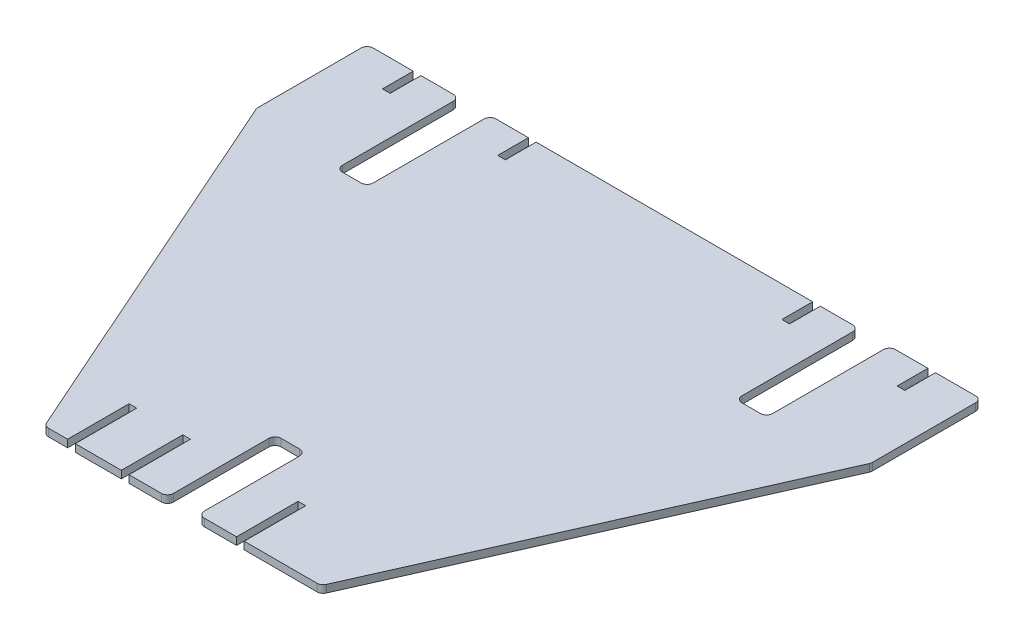
SolidWorks part; units mm, degrees
material "Corrugated Paper"
ref_plane "Front Plane" through (0, 0, 0) normal (0, 0, 1) x (1, 0, 0)
ref_plane "Top Plane" through (0, 0, 0) normal (0, 1, 0) x (1, 0, 0)
ref_plane "Right Plane" through (0, 0, 0) normal (1, 0, 0) x (0, 0, -1)
sketch "Sketch1" plane through (0, 0, 0) normal (0, 1, 0) x (1, 0, 0)
  line L0 (0, 0) -> (0, -142.875) construction
  line L1 (6.35, -57.15) -> (-6.35, -57.15)
  line L2 (-6.35, -57.15) -> (-6.35, -101.6)
  line L3 (-6.35, -101.6) -> (-22.225, -101.6)
  line L4 (-57.15, -101.6) -> (-127, 55.88)
  line L5 (-127, 55.88) -> (-127, 101.6)
  line L6 (-127, 101.6) -> (-107.95, 101.6)
  line L7 (-88.9, 101.6) -> (-88.9, 50.8)
  line L9 (-88.9, 50.8) -> (-76.2, 50.8)
  line L10 (-76.2, 50.8) -> (-76.2, 101.6)
  line L11 (-76.2, 101.6) -> (-60.325, 101.6)
  line L13 (76.2, 50.8) -> (76.2, 101.6)
  line L14 (88.9, 50.8) -> (76.2, 50.8)
  line L15 (88.9, 101.6) -> (88.9, 50.8)
  line L16 (127, 101.6) -> (107.95, 101.6)
  line L17 (127, 55.88) -> (127, 101.6)
  line L18 (57.15, -101.6) -> (127, 55.88)
  line L19 (6.35, -101.6) -> (22.225, -101.6)
  line L20 (6.35, -57.15) -> (6.35, -101.6)
  line L21 (-127, 101.6) -> (127, -101.6) construction
  line L22 (-25.4, -101.6) -> (-44.45, -101.6)
  line L24 (-25.4, -101.6) -> (-25.4, -76.2)
  line L25 (-25.4, -76.2) -> (-22.225, -76.2)
  line L26 (-22.225, -101.6) -> (-22.225, -76.2)
  line L27 (25.4, -101.6) -> (25.4, -76.2)
  line L28 (25.4, -76.2) -> (22.225, -76.2)
  line L29 (22.225, -101.6) -> (22.225, -76.2)
  line L30 (25.4, -101.6) -> (57.15, -101.6)
  line L31 (-82.55, 50.8) -> (-82.55, 101.6) construction
  line L32 (-104.775, 101.6) -> (-88.9, 101.6)
  line L34 (-107.95, 101.6) -> (-107.95, 88.9)
  line L35 (-107.95, 88.9) -> (-104.775, 88.9)
  line L36 (-104.775, 101.6) -> (-104.775, 88.9)
  line L37 (-57.15, 101.6) -> (-57.15, 88.9)
  line L38 (-57.15, 88.9) -> (-60.325, 88.9)
  line L39 (-60.325, 101.6) -> (-60.325, 88.9)
  line L40 (-57.15, 101.6) -> (57.15, 101.6)
  line L41 (107.95, 101.6) -> (107.95, 88.9)
  line L42 (107.95, 88.9) -> (104.775, 88.9)
  line L43 (104.775, 101.6) -> (104.775, 88.9)
  line L44 (57.15, 101.6) -> (57.15, 88.9)
  line L45 (60.325, 101.6) -> (60.325, 88.9)
  line L46 (57.15, 88.9) -> (60.325, 88.9)
  line L47 (60.325, 101.6) -> (76.2, 101.6)
  line L48 (104.775, 101.6) -> (88.9, 101.6)
  line L49 (-47.625, -101.6) -> (-47.625, -76.2)
  line L50 (-47.625, -76.2) -> (-44.45, -76.2)
  line L51 (-44.45, -76.2) -> (-44.45, -101.6)
  line L52 (-47.625, -101.6) -> (-57.15, -101.6)
  point P26 (0, -57.15)
  dimension "D2" = 12.7
  dimension "D3" = 254
  dimension "D5" = 44.45
  dimension "D6" = 50.8
  dimension "D7" = 203.2
  dimension "D8" = 45.72
  dimension "D10" = 3.175
  dimension "D11" = 25.4
  dimension "D12" = 3.175
  dimension "D4" = 114.3
  dimension "D13" = 50.8
  dimension "D9" = 50.8
  dimension "D14" = 38.1
  dimension "D15" = 12.7
  dimension "D16" = 19.05
extrude "Boss-Extrude1" add sketch "Sketch1" along normal blind 3.0988 contours L13 L47 L45 L46 L44 L40 L37 L38 L39 L11 L10 L9 L7 L32 L36 L35 L34 L6 L5 L4 L52 L49 L50 L51 L22 L24 L25 L26 L3 L2 L1 L20 L19 L29 L28 L27 L30 L18 L17 L16 L41 L42 L43 L48 L15 L14
fillet "Fillet1" radius 2.54 18 edges at (88.9, 1.5494, -50.8) (88.9, 1.5494, -101.6) (6.35, 1.5494, 101.6) (6.35, 1.5494, 57.15) (-6.35, 1.5494, 57.15) (-6.35, 1.5494, 101.6) (-127, 1.5494, -55.88) (-127, 1.5494, -101.6) (-88.9, 1.5494, -101.6) (-88.9, 1.5494, -50.8) (-76.2, 1.5494, -50.8) (-76.2, 1.5494, -101.6) (76.2, 1.5494, -101.6) (76.2, 1.5494, -50.8) (127, 1.5494, -101.6) (127, 1.5494, -55.88) (57.15, 1.5494, 101.6) (-57.15, 1.5494, 101.6)
sketch "Sketch4" plane through (0, 3.0988, 0) normal (0, 1, 0) x (1, 0, 0)
  line L0 (0, -164.31) -> (0, 101.6) construction
  line L1 (-63.105, 101.6) -> (63.105, 101.6) construction
  line L2 (-63.105, 101.6) -> (-63.105, -164.31) construction
  line L3 (-63.105, -164.31) -> (63.105, -164.31) construction
  line L4 (63.105, 101.6) -> (63.105, -164.31) construction
  line L5 (57.8198, -100.0899) -> (126.7819, 55.3882) construction
  line L6 (65.3301, -83.1577) -> (50.405, -83.1577)
  line L7 (65.3301, -83.1577) -> (65.3301, -88.1742)
  line L8 (65.3301, -88.1742) -> (50.405, -88.1742)
  line L9 (50.405, -83.1577) -> (50.405, -88.1742)
  line L10 (-50.405, -83.1577) -> (-50.405, -88.1742)
  line L11 (-65.3301, -88.1742) -> (-50.405, -88.1742)
  line L12 (-65.3301, -83.1577) -> (-65.3301, -88.1742)
  line L13 (-65.3301, -83.1577) -> (-50.405, -83.1577)
  line L14 (-57.15, 101.6) -> (57.15, 101.6) construction
  line L15 (-1.5875, 101.6) -> (1.5875, 101.6)
  line L16 (-1.5875, 101.6) -> (-1.5875, 88.9)
  line L17 (-1.5875, 88.9) -> (1.5875, 88.9)
  line L18 (1.5875, 101.6) -> (1.5875, 88.9)
  point P8 (63.105, -88.1742)
  point P11 (0, 101.6)
  point P24 (0, 0)
  dimension "D1" = 265.91
  dimension "D2" = 126.21
  dimension "D5" = 3.175
  dimension "D6" = 12.7
  dimension "D4" = 12.7
  dimension "D3" = 5.0165
extrude "Cut-Extrude3" [suppressed] cut sketch "Sketch4" against normal through all
equation "\"D1@Boss-Extrude1\" = \"thick\""
equation "\"D10@Sketch1\"=\"thick\"+\"clear\""
equation "\"D12@Sketch1\"=\"thick\"+\"clear\""
equation "\"rodThick\"= 0.085in"
equation "\"thick\"= 0.122in"
equation "\"clear\"= 0.003in"
equation "\"D5@Sketch4\"=\"thick\"+\"clear\""
